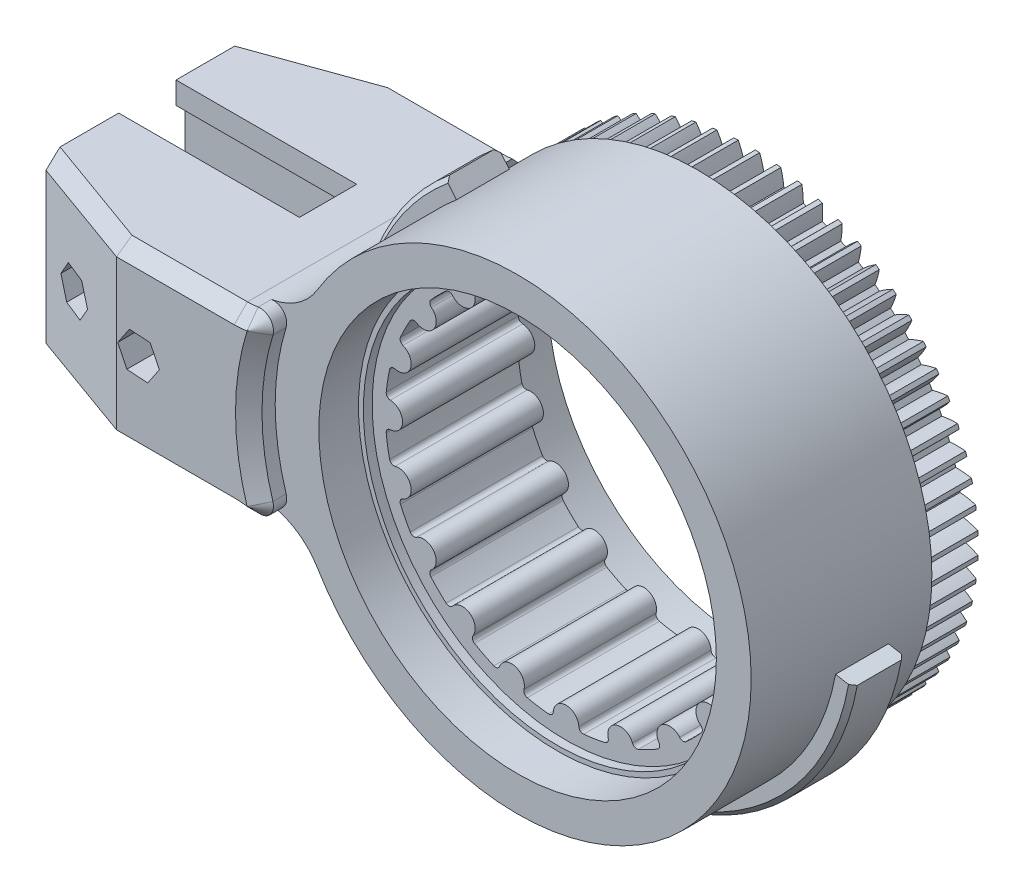
SolidWorks part; units mm, degrees
ref_plane "Front Plane" through (0, 0, 0) normal (0, 0, 1) x (1, 0, 0)
ref_plane "Top Plane" through (0, 0, 0) normal (0, 1, 0) x (1, 0, 0)
ref_plane "Right Plane" through (0, 0, 0) normal (1, 0, 0) x (0, 0, -1)
sketch "Sketch1" plane through (0, 0, 0) normal (0, 0, 1) x (1, 0, 0)
  circle A0 centre (0, 0) radius 53
  dimension "D1" = 106
extrude "Boss-Extrude1" add sketch "Sketch1" along normal blind 30
sketch "Sketch4" plane through (0, 0, 0) normal (0, 0, -1) x (-1, 0, 0)
  line L0 (53, 0) -> (110, 0) construction
  line L1 (49.0816, -20) -> (110, -20)
  line L2 (49.0816, 20) -> (110, 20)
  line L3 (110, 20) -> (110, -20)
  line L4 (0, 20) -> (110, 20) construction
  line L5 (0, 0) -> (110, 0) construction
  line L6 (0, -20) -> (110, -20) construction
  circle A0 centre (0, 0) radius 53 construction
  arc A1 (49.0816, -20) -> (49.0816, 20) centre (0, 0) ccw
  dimension "D3" = 110
  dimension "D1" = 20
  dimension "D2" = 20
extrude "Boss-Extrude2" add sketch "Sketch4" against normal up to surface (30 mm away) up to face at (53, 0, 30)
sketch "Sketch5" plane through (0, 0, 0) normal (0, 0, -1) x (-1, 0, 0)
  line L2 (110, -20) -> (110, 20)
  line L3 (110, 20) -> (51.2348, 20)
  line L5 (51.2348, -20) -> (110, -20)
  line L6 (0, 0) -> (139.0391, 0) construction
  arc A0 (51.2348, -20) -> (51.2348, 20) centre (0, 0) ccw
  dimension "D1" = 110
  dimension "D2" = 40
  dimension "D3" = 110
extrude "Boss-Extrude3" add sketch "Sketch5" along normal blind 17
sketch "Sketch6" plane through (0, 0, 30) normal (0, 0, 1) x (1, 0, 0)
  line L0 (-110, 0) -> (0, 0) construction
  line L6 (-110, -20) -> (-51.2348, -20)
  line L7 (-110, 20) -> (-110, -20)
  line L8 (-51.2348, 20) -> (-110, 20)
  arc A2 (-51.2348, 20) -> (-51.2348, -20) centre (0, 0) ccw
  dimension "D1" = 55
  dimension "D2" = 40
  dimension "D3" = 110
extrude "Boss-Extrude4" add sketch "Sketch6" along normal blind 17
sketch "Sketch7" plane through (0, 20, 0) normal (0, 1, 0) x (1, 0, 0)
  line L0 (53, -15) -> (-110, -15) construction
  line L1 (53, -30) -> (53, 0) construction
  line L2 (-110, -47) -> (-110, 17) construction
  line L4 (-151, -8.5) -> (-69, -8.5)
  line L5 (-151, -8.5) -> (-151, -21.5)
  line L6 (-151, -21.5) -> (-69, -21.5)
  line L7 (-69, -8.5) -> (-69, -21.5)
  line L8 (-151, -8.5) -> (-69, -21.5) construction
  line L9 (-151, -21.5) -> (-69, -8.5) construction
  dimension "D1" = 13
  dimension "D2" = 41
extrude "Cut-Extrude3" cut sketch "Sketch7" against normal through all
sketch "Sketch8" plane through (0, 20, 0) normal (0, 1, 0) x (1, 0, 0)
  line L0 (-110, 8) -> (-85, 17)
  line L1 (-110, -8.5) -> (-110, 17) construction
  line L2 (-110, 17) -> (-51.2348, 17) construction
  line L3 (-69, -15) -> (-102.4865, -15) construction
  line L4 (-69, -21.5) -> (-69, -8.5) construction
  line L5 (-110, -38) -> (-85, -47)
  line L6 (-110, -47) -> (-110, -21.5) construction
  line L7 (-51.2348, -47) -> (-110, -47) construction
  line L8 (-110, 17) -> (-85, 17)
  line L9 (-110, 8) -> (-110, 17)
  line L10 (-110, -47) -> (-110, -38)
  line L11 (-85, -47) -> (-110, -47)
  dimension "D1" = 9
  dimension "D2" = 25
extrude "Cut-Extrude4" cut sketch "Sketch8" against normal through all
fillet "Fillet3" radius 15 2 edges at (-49.0816, 20, 15) (-49.0816, -20, 15)
sketch "Sketch10" plane through (-110, 0, 0) normal (-1, 0, 0) x (0, 0, 1)
  line L0 (15, 20) -> (15, -20) construction
  line L1 (47, 20) -> (-17, 20) construction
  line L2 (-17, -20) -> (47, -20) construction
  line L3 (21.5, -20) -> (21.5, 20) construction
  line L4 (6.5, 15) -> (23.5, 15)
  line L5 (6.5, 15) -> (6.5, -15)
  line L6 (6.5, -15) -> (23.5, -15)
  line L7 (23.5, 15) -> (23.5, -15)
  line L8 (6.5, 15) -> (23.5, -15) construction
  line L9 (6.5, -15) -> (23.5, 15) construction
  point P6 (15, 0)
  dimension "D1" = 30
  dimension "D2" = 2
extrude "Cut-Extrude5" cut sketch "Sketch10" against normal blind 41
sketch "Sketch11" plane through (0, 0, -17) normal (0, 0, -1) x (-1, 0, 0)
  line L0 (110, 0) -> (45.4033, 0) construction
  line L1 (110, -20) -> (110, 20) construction
  circle A0 centre (100, 0) radius 2.75
  circle A1 centre (80, 0) radius 2.75
  dimension "D3" = 5.5
  dimension "D1" = 10
  dimension "D2" = 20
extrude "Cut-Extrude6" cut sketch "Sketch11" against normal through all
sketch "Sketch12" plane through (0, 0, -17) normal (0, 0, -1) x (-1, 0, 0)
  circle A0 centre (80, 0) radius 4.6
  circle A1 centre (100, 0) radius 4.6
  dimension "D1" = 9.2
extrude "Cut-Extrude7" cut sketch "Sketch12" against normal blind 12
sketch "Sketch13" plane through (0, 0, 47) normal (0, 0, 1) x (1, 0, 0)
  line L1 (-104.7224, 0.3346) -> (-102.651, -3.9225)
  line L2 (-102.651, -3.9225) -> (-97.9285, -4.257)
  line L3 (-97.9285, -4.257) -> (-95.2776, -0.3346)
  line L4 (-95.2776, -0.3346) -> (-97.349, 3.9225)
  line L5 (-97.349, 3.9225) -> (-102.0715, 4.257)
  line L6 (-102.0715, 4.257) -> (-104.7224, 0.3346)
  line L7 (-84.7224, 0.3346) -> (-82.651, -3.9225)
  line L8 (-82.651, -3.9225) -> (-77.9285, -4.257)
  line L9 (-77.9285, -4.257) -> (-75.2776, -0.3346)
  line L10 (-75.2776, -0.3346) -> (-77.349, 3.9225)
  line L11 (-77.349, 3.9225) -> (-82.0715, 4.257)
  line L12 (-82.0715, 4.257) -> (-84.7224, 0.3346)
  circle A0 centre (-100, 0) radius 4.1 construction
  circle A1 centre (-80, 0) radius 4.1 construction
  dimension "D1" = 8.2
extrude "Cut-Extrude8" cut sketch "Sketch13" against normal blind 12
sketch3d "3DSketch1"
  line L0 (-58.3009, 20, 47) -> (-85, 20, 47) construction
  line L1 (-85, -20, 47) -> (-85, 20, 47) construction
  point P0 (-54.8705, 20, 47)
  point P1 (-85, 11.3679, 47)
  point P4 (-110, 20, 38)
ref_plane "Plane2" through (0, 0, 15) normal (0, 0, 1) x (1, 0, 0)
fillet "Fillet5" radius 3 4 edges at (-50.2597, -22.3375, -8.5) (-50.2597, -22.3375, 38.5) (-50.2597, 22.3375, -8.5) (-50.2597, 22.3375, 38.5)
sketch "Sketch25" plane through (0, 0, 15) normal (0, 0, 1) x (1, 0, 0)
  circle A0 centre (0, 0) radius 57
  circle A1 centre (0, 0) radius 53
  arc A2 (-45.4404, -27.2794) -> (-45.4404, 27.2794) centre (0, 0) ccw construction
  dimension "D1" = 4
extrude "Boss-Extrude8" add sketch "Sketch25" along normal mid plane 12
sketch "Sketch26" plane through (0, 0, 21) normal (0, 0, 1) x (1, 0, 0)
  line L0 (56.0861, -10.1662) -> (52.1502, -9.4528)
  line L2 (-36.4297, 43.8392) -> (-33.8733, 40.7627)
  arc A0 (-53.0039, -20.9664) -> (-53.0039, 20.9664) centre (0, 0) ccw construction
  arc A1 (-45.4404, -27.2794) -> (-45.4404, 27.2794) centre (0, 0) ccw construction
  arc A2 (56.0861, -10.1662) -> (-36.4297, 43.8392) centre (0, 0) ccw
  arc A3 (52.1502, -9.4528) -> (-33.8733, 40.7627) centre (0, 0) ccw
  dimension "D1" = 140
extrude "Cut-Extrude12" cut sketch "Sketch26" against normal blind 15
chamfer "Chamfer4" distance 1 angle 45 4 edges at (5.6157, -56.7227, 21) (5.6157, -56.7227, 9) (-46.1561, 33.4457, 9) (-46.1561, 33.4457, 21)
sketch "Sketch27" plane through (0, 0, 30) normal (0, 0, 1) x (1, 0, 0)
  circle A0 centre (0, 0) radius 40 construction
  arc A1 (-40.9074, -2.7544) -> (-40.9074, 2.7544) centre (-40, 0) ccw
  arc A2 (-39.7564, 10.0215) -> (-38.0541, 15.2607) centre (-38.0423, 12.3607) ccw
  arc A3 (-34.7138, 21.8164) -> (-31.4758, 26.2731) centre (-32.3607, 23.5114) ccw
  arc A4 (-26.2731, 31.4758) -> (-21.8164, 34.7138) centre (-23.5114, 32.3607) ccw
  arc A5 (-15.2607, 38.0541) -> (-10.0215, 39.7564) centre (-12.3607, 38.0423) ccw
  arc A6 (-2.7544, 40.9074) -> (2.7544, 40.9074) centre (0, 40) ccw
  arc A7 (10.0215, 39.7564) -> (15.2607, 38.0541) centre (12.3607, 38.0423) ccw
  arc A8 (21.8164, 34.7138) -> (26.2731, 31.4758) centre (23.5114, 32.3607) ccw
  arc A9 (31.4758, 26.2731) -> (34.7138, 21.8164) centre (32.3607, 23.5114) ccw
  arc A10 (38.0541, 15.2607) -> (39.7564, 10.0215) centre (38.0423, 12.3607) ccw
  arc A11 (40.9074, 2.7544) -> (40.9074, -2.7544) centre (40, 0) ccw
  arc A12 (39.7564, -10.0215) -> (38.0541, -15.2607) centre (38.0423, -12.3607) ccw
  arc A13 (34.7138, -21.8164) -> (31.4758, -26.2731) centre (32.3607, -23.5114) ccw
  arc A14 (26.2731, -31.4758) -> (21.8164, -34.7138) centre (23.5114, -32.3607) ccw
  arc A15 (15.2607, -38.0541) -> (10.0215, -39.7564) centre (12.3607, -38.0423) ccw
  arc A16 (2.7544, -40.9074) -> (-2.7544, -40.9074) centre (0, -40) ccw
  arc A17 (26.2731, -31.4758) -> (31.4758, -26.2731) centre (0, 0) ccw
  arc A18 (34.7138, -21.8164) -> (38.0541, -15.2607) centre (0, 0) ccw
  arc A19 (39.7564, -10.0215) -> (40.9074, -2.7544) centre (0, 0) ccw
  arc A20 (40.9074, 2.7544) -> (39.7564, 10.0215) centre (0, 0) ccw
  arc A21 (38.0541, 15.2607) -> (34.7138, 21.8164) centre (0, 0) ccw
  arc A22 (31.4758, 26.2731) -> (26.2731, 31.4758) centre (0, 0) ccw
  arc A23 (21.8164, 34.7138) -> (15.2607, 38.0541) centre (0, 0) ccw
  arc A24 (10.0215, 39.7564) -> (2.7544, 40.9074) centre (0, 0) ccw
  arc A25 (-2.7544, 40.9074) -> (-10.0215, 39.7564) centre (0, 0) ccw
  arc A26 (-15.2607, 38.0541) -> (-21.8164, 34.7138) centre (0, 0) ccw
  arc A27 (-26.2731, 31.4758) -> (-31.4758, 26.2731) centre (0, 0) ccw
  arc A28 (-34.7138, 21.8164) -> (-38.0541, 15.2607) centre (0, 0) ccw
  arc A29 (-39.7564, 10.0215) -> (-40.9074, 2.7544) centre (0, 0) ccw
  arc A30 (-40.9074, -2.7544) -> (-2.7544, -40.9074) centre (0, 0) ccw
  arc A31 (2.7544, -40.9074) -> (10.0215, -39.7564) centre (0, 0) ccw
  arc A32 (15.2607, -38.0541) -> (21.8164, -34.7138) centre (0, 0) ccw
  arc A33 (-10.0215, -39.7564) -> (-15.2607, -38.0541) centre (-12.3607, -38.0423) ccw
  arc A34 (-21.8164, -34.7138) -> (-26.2731, -31.4758) centre (-23.5114, -32.3607) ccw
  arc A35 (-31.4758, -26.2731) -> (-34.7138, -21.8164) centre (-32.3607, -23.5114) ccw
  arc A36 (-38.0541, -15.2607) -> (-39.7564, -10.0215) centre (-38.0423, -12.3607) ccw
  point P35 (0, 0)
  point P38 (0, 0)
  dimension "D1" = 80
  dimension "D2" = 5.8
  dimension "D4" = 41
  dimension "D3" = 20
extrude "Cut-Extrude13" cut sketch "Sketch27" against normal through all contours A36 A30 A35 A34 A33 A16 A31 A15 A32 A14 A17 A13 A18 A12 A19 A11 A20 A10 A21 A9 A22 A8 A23 A7 A24 A6 A25 A5 A26 A4 A27 A3 A28 A2 A29 A1 region at (0, 0, 30)
fillet "Fillet6" radius 1 40 edges at (2.7544, 40.9074, 15) (38.0541, -15.2607, 15) (31.4758, -26.2731, 15) (21.8164, -34.7138, 15) (10.0215, -39.7564, 15) (-2.7544, -40.9074, 15) (-15.2607, -38.0541, 15) (-26.2731, -31.4758, 15) (-34.7138, -21.8164, 15) (-40.9074, 2.7544, 15) (-40.9074, -2.7544, 15) (-39.7564, 10.0215, 15) (-38.0541, 15.2607, 15) (-31.4758, 26.2731, 15) (-34.7138, 21.8164, 15) (-26.2731, 31.4758, 15) (-21.8164, 34.7138, 15) (-10.0215, 39.7564, 15) (-15.2607, 38.0541, 15) (-2.7544, 40.9074, 15) (10.0215, 39.7564, 15) (15.2607, 38.0541, 15) (21.8164, 34.7138, 15) (26.2731, 31.4758, 15) (31.4758, 26.2731, 15) (34.7138, 21.8164, 15) (38.0541, 15.2607, 15) (39.7564, 10.0215, 15) (40.9074, 2.7544, 15) (40.9074, -2.7544, 15) (39.7564, -10.0215, 15) (34.7138, -21.8164, 15) (26.2731, -31.4758, 15) (-39.7564, -10.0215, 15) (15.2607, -38.0541, 15) (2.7544, -40.9074, 15) (-10.0215, -39.7564, 15) (-21.8164, -34.7138, 15) (-31.4758, -26.2731, 15) (-38.0541, -15.2607, 15)
sketch "Sketch28" plane through (0, 0, 30) normal (0, 0, 1) x (1, 0, 0)
  arc A0 (-45.4404, 27.2794) -> (-45.4404, -27.2794) centre (0, 0) ccw
  arc A7 (-52.5145, 16.3471) -> (-52.5145, -16.3471) centre (0, 0) ccw
  arc A8 (-55.8659, -20.199) -> (-52.5145, -16.3471) centre (-55.3789, -17.2388) ccw
  arc A9 (-45.4404, -27.2794) -> (-55.8659, -20.199) centre (-58.3009, -35) ccw
  arc A10 (-45.4404, -27.2794) -> (-45.4404, 27.2794) centre (0, 0) ccw
  arc A11 (-55.8659, 20.199) -> (-45.4404, 27.2794) centre (-58.3009, 35) ccw
  arc A12 (-52.5145, 16.3471) -> (-55.8659, 20.199) centre (-55.3789, 17.2388) ccw
  arc A13 (-52.5145, 16.3471) -> (-52.5145, -16.3471) centre (0, 0) ccw
  arc A14 (-55.8659, -20.199) -> (-52.5145, -16.3471) centre (-55.3789, -17.2388) ccw
  arc A15 (-45.4404, -27.2794) -> (-55.8659, -20.199) centre (-58.3009, -35) ccw
  arc A17 (-55.8659, 20.199) -> (-45.4404, 27.2794) centre (-58.3009, 35) ccw
  arc A18 (-52.5145, 16.3471) -> (-55.8659, 20.199) centre (-55.3789, 17.2388) ccw
  dimension "D1" = 0
extrude "Boss-Extrude9" add sketch "Sketch28" along normal up to surface (17 mm away) up to face at (-80, 0, 47)
sketch "Sketch29" plane through (0, 0, 30) normal (0, 0, 1) x (1, 0, 0)
  circle A0 centre (0, 0) radius 53
  circle A1 centre (0, 0) radius 44
  arc A2 (-45.4404, -27.2794) -> (-45.4404, 27.2794) centre (0, 0) ccw construction
  dimension "D1" = 88
extrude "Boss-Extrude10" add sketch "Sketch29" along normal blind 11
sketch "Sketch30" plane through (0, 0, 41) normal (0, 0, 1) x (1, 0, 0)
  circle A0 centre (0, 0) radius 45.1
  dimension "D1" = 90.2
extrude "Cut-Extrude14" cut sketch "Sketch30" against normal blind 9
sketch "Sketch31" plane through (0, 0, 0) normal (0, 0, -1) x (-1, 0, 0)
  arc A6 (52.5145, -16.3471) -> (52.5145, 16.3471) centre (0, 0) ccw
  arc A7 (55.8659, 20.199) -> (52.5145, 16.3471) centre (55.3789, 17.2388) ccw
  arc A8 (45.4404, 27.2794) -> (55.8659, 20.199) centre (58.3009, 35) ccw
  arc A9 (45.4404, 27.2794) -> (45.4404, -27.2794) centre (0, 0) ccw
  arc A10 (55.8659, -20.199) -> (45.4404, -27.2794) centre (58.3009, -35) ccw
  arc A11 (52.5145, -16.3471) -> (55.8659, -20.199) centre (55.3789, -17.2388) ccw
  arc A12 (52.5145, -16.3471) -> (52.5145, 16.3471) centre (0, 0) ccw
  arc A13 (55.8659, 20.199) -> (52.5145, 16.3471) centre (55.3789, 17.2388) ccw
  arc A14 (45.4404, 27.2794) -> (55.8659, 20.199) centre (58.3009, 35) ccw
  arc A15 (45.4404, 27.2794) -> (45.4404, -27.2794) centre (0, 0) ccw
  arc A16 (55.8659, -20.199) -> (45.4404, -27.2794) centre (58.3009, -35) ccw
  arc A17 (52.5145, -16.3471) -> (55.8659, -20.199) centre (55.3789, -17.2388) ccw
  circle A24 centre (0, 0) radius 44
  dimension "D2" = 88
  dimension "D1" = 0
extrude "Boss-Extrude12" add sketch "Sketch31" along normal blind 11
sketch "Sketch32" plane through (0, 0, -11) normal (0, 0, -1) x (-1, 0, 0)
  circle A0 centre (0, 0) radius 45.1
  dimension "D1" = 90.2
extrude "Cut-Extrude15" cut sketch "Sketch32" against normal blind 9
sketch "Sketch33" plane through (0, 0, 41) normal (0, 0, 1) x (1, 0, 0)
  arc A6 (-55.8659, -20.199) -> (-52.5145, -16.3471) centre (-55.3789, -17.2388) ccw
  arc A7 (-52.5145, 16.3471) -> (-52.5145, -16.3471) centre (0, 0) ccw
  arc A8 (-52.5145, 16.3471) -> (-55.8659, 20.199) centre (-55.3789, 17.2388) ccw
  arc A9 (-55.8659, 20.199) -> (-45.4404, 27.2794) centre (-58.3009, 35) ccw
  arc A10 (-45.4404, -27.2794) -> (-45.4404, 27.2794) centre (0, 0) ccw
  arc A11 (-45.4404, -27.2794) -> (-55.8659, -20.199) centre (-58.3009, -35) ccw
  arc A12 (-55.8659, -20.199) -> (-52.5145, -16.3471) centre (-55.3789, -17.2388) ccw
  arc A13 (-52.5145, 16.3471) -> (-52.5145, -16.3471) centre (0, 0) ccw
  arc A14 (-52.5145, 16.3471) -> (-55.8659, 20.199) centre (-55.3789, 17.2388) ccw
  arc A15 (-55.8659, 20.199) -> (-45.4404, 27.2794) centre (-58.3009, 35) ccw
  arc A16 (-45.4404, -27.2794) -> (-45.4404, 27.2794) centre (0, 0) ccw
  arc A17 (-45.4404, -27.2794) -> (-55.8659, -20.199) centre (-58.3009, -35) ccw
  dimension "D1" = 0
extrude "Cut-Extrude16" cut sketch "Sketch33" along normal blind 87
sketch "Sketch34" plane through (0, 0, -11) normal (0, 0, -1) x (-1, 0, 0)
  line L0 (43.5903, -29.2582) -> (46.7331, -25.4509)
  line L1 (43.0288, 30.0782) -> (46.5882, 25.6292)
  line L2 (-0.0007, 0.0006) -> (24.1488, 0.0006) construction
  line L3 (43.0288, -30.077) -> (46.5882, -25.628)
  line L4 (46.7331, -25.4509) -> (28.204, -92.7872)
  line L5 (28.204, -92.7872) -> (-81.3353, -44.683)
  line L6 (-81.3353, -44.683) -> (-81.3353, 38.0689)
  line L7 (-81.3353, 38.0689) -> (11.5354, 66.4741)
  line L8 (11.5354, 66.4741) -> (65.3005, 45.6222)
  line L9 (65.3005, 45.6222) -> (46.5882, 25.6292)
  circle A0 centre (-0.0007, 0.0006) radius 51 construction
  arc A1 (-49.1207, -0.6313) -> (-52.4653, -1.928) centre (-43.4473, -20.2265) ccw
  arc A2 (-52.4653, -1.928) -> (-52.4194, -2.9198) centre (-0.0007, 0.0006) ccw
  arc A3 (-52.4194, -2.9198) -> (-48.9694, -3.9024) centre (-45.1283, 16.1327) ccw
  arc A4 (-48.9694, -3.9024) -> (-48.8528, -5.1608) centre (-0.0007, 0.0006) ccw
  arc A5 (-48.8528, -5.1608) -> (-52.0635, -6.7606) centre (-41.3956, -24.149) ccw
  arc A6 (-52.0635, -6.7606) -> (-51.9264, -7.744) centre (-0.0007, 0.0006) ccw
  arc A7 (-51.9264, -7.744) -> (-48.4004, -8.404) centre (-46.4243, 11.9) ccw
  arc A8 (-48.4004, -8.404) -> (-48.1682, -9.6463) centre (-0.0007, 0.0006) ccw
  arc A9 (-48.1682, -9.6463) -> (-51.2176, -11.5355) centre (-38.9908, -27.8654) ccw
  arc A10 (-51.2176, -11.5355) -> (-50.9903, -12.502) centre (-0.0007, 0.0006) ccw
  arc A11 (-50.9903, -12.502) -> (-47.4185, -12.8339) centre (-47.3242, 7.5659) ccw
  arc A12 (-47.4185, -12.8339) -> (-47.0726, -14.0495) centre (-0.0007, 0.0006) ccw
  arc A13 (-47.0726, -14.0495) -> (-49.9347, -16.212) centre (-36.2533, -31.3441) ccw
  arc A14 (-49.9347, -16.212) -> (-49.6192, -17.1534) centre (-0.0007, 0.0006) ccw
  arc A15 (-49.6192, -17.1534) -> (-46.032, -17.1543) centre (-47.8203, 3.1671) ccw
  arc A16 (-46.032, -17.1543) -> (-45.5754, -18.3328) centre (-0.0007, 0.0006) ccw
  arc A17 (-45.5754, -18.3328) -> (-48.2258, -20.7502) centre (-33.2066, -34.5553) ccw
  arc A18 (-48.2258, -20.7502) -> (-47.8247, -21.6584) centre (-0.0007, 0.0006) ccw
  arc A19 (-47.8247, -21.6584) -> (-44.2528, -21.3284) centre (-47.9085, -1.2586) ccw
  arc A20 (-44.2528, -21.3284) -> (-43.6894, -22.4597) centre (-0.0007, 0.0006) ccw
  arc A21 (-43.6894, -22.4597) -> (-46.1054, -25.1113) centre (-29.8765, -37.4718) ccw
  arc A22 (-46.1054, -25.1113) -> (-45.6223, -25.9787) centre (-0.0007, 0.0006) ccw
  arc A23 (-45.6223, -25.9787) -> (-42.096, -25.3205) centre (-47.588, -5.6736) ccw
  arc A24 (-42.096, -25.3205) -> (-41.4307, -26.395) centre (-0.0007, 0.0006) ccw
  arc A25 (-41.4307, -26.395) -> (-43.5917, -29.2582) centre (-26.2915, -40.0685) ccw
  arc A26 (-43.5917, -29.2582) -> (-43.0306, -30.0773) centre (-0.0007, 0.0006) ccw
  arc A27 (-43.0306, -30.0773) -> (-39.5801, -29.0965) centre (-46.8614, -10.0402) ccw
  arc A28 (-39.5801, -29.0965) -> (-38.8185, -30.105) centre (-0.0007, 0.0006) ccw
  arc A29 (-38.8185, -30.105) -> (-40.7061, -33.1554) centre (-22.4823, -42.3234) ccw
  arc A30 (-40.7061, -33.1554) -> (-40.0718, -33.9193) centre (-0.0007, 0.0006) ccw
  arc A31 (-40.0718, -33.9193) -> (-36.7265, -32.6243) centre (-45.7351, -14.3211) ccw
  arc A32 (-36.7265, -32.6243) -> (-35.8751, -33.5583) centre (-0.0007, 0.0006) ccw
  arc A33 (-35.8751, -33.5583) -> (-37.4732, -36.7698) centre (-18.4812, -44.2172) ccw
  arc A34 (-37.4732, -36.7698) -> (-36.7711, -37.4719) centre (-0.0007, 0.0006) ccw
  arc A35 (-36.7711, -37.4719) -> (-33.5596, -35.8738) centre (-44.2185, -18.4799) ccw
  arc A36 (-33.5596, -35.8738) -> (-32.6256, -36.7252) centre (-0.0007, 0.0006) ccw
  arc A37 (-32.6256, -36.7252) -> (-33.9206, -40.0705) centre (-14.3225, -45.7337) ccw
  arc A38 (-33.9206, -40.0705) -> (-33.1568, -40.7048) centre (-0.0007, 0.0006) ccw
  arc A39 (-33.1568, -40.7048) -> (-30.1064, -38.8171) centre (-42.3247, -22.4809) ccw
  arc A40 (-30.1064, -38.8171) -> (-29.0978, -39.5788) centre (-0.0007, 0.0006) ccw
  arc A41 (-29.0978, -39.5788) -> (-30.0786, -43.0293) centre (-10.0415, -46.8601) ccw
  arc A42 (-30.0786, -43.0293) -> (-29.2595, -43.5904) centre (-0.0007, 0.0006) ccw
  arc A43 (-29.2595, -43.5904) -> (-26.3963, -41.4294) centre (-40.0699, -26.2902) ccw
  arc A44 (-26.3963, -41.4294) -> (-25.3218, -42.0947) centre (-0.0007, 0.0006) ccw
  arc A45 (-25.3218, -42.0947) -> (-25.98, -45.6209) centre (-5.675, -47.5866) ccw
  arc A46 (-25.98, -45.6209) -> (-25.1126, -46.1041) centre (-0.0007, 0.0006) ccw
  arc A47 (-25.1126, -46.1041) -> (-22.461, -43.6881) centre (-37.4731, -29.8752) ccw
  arc A48 (-22.461, -43.6881) -> (-21.3297, -44.2514) centre (-0.0007, 0.0006) ccw
  arc A49 (-21.3297, -44.2514) -> (-21.6598, -47.8234) centre (-1.26, -47.9072) ccw
  arc A50 (-21.6598, -47.8234) -> (-20.7515, -48.2244) centre (-0.0007, 0.0006) ccw
  arc A51 (-20.7515, -48.2244) -> (-18.3341, -45.5741) centre (-34.5567, -33.2052) ccw
  arc A52 (-18.3341, -45.5741) -> (-17.1557, -46.0306) centre (-0.0007, 0.0006) ccw
  arc A53 (-17.1557, -46.0306) -> (-17.1547, -49.6178) centre (3.1658, -47.819) ccw
  arc A54 (-17.1547, -49.6178) -> (-16.2133, -49.9334) centre (-0.0007, 0.0006) ccw
  arc A55 (-16.2133, -49.9334) -> (-14.0508, -47.0713) centre (-31.3454, -36.252) ccw
  arc A56 (-14.0508, -47.0713) -> (-12.8353, -47.4171) centre (-0.0007, 0.0006) ccw
  arc A57 (-12.8353, -47.4171) -> (-12.5034, -50.9889) centre (7.5645, -47.3228) ccw
  arc A58 (-12.5034, -50.9889) -> (-11.5368, -51.2163) centre (-0.0007, 0.0006) ccw
  arc A59 (-11.5368, -51.2163) -> (-9.6476, -48.1669) centre (-27.8667, -38.9895) ccw
  arc A60 (-9.6476, -48.1669) -> (-8.4054, -48.3991) centre (-0.0007, 0.0006) ccw
  arc A61 (-8.4054, -48.3991) -> (-7.7453, -51.925) centre (11.8987, -46.4229) ccw
  arc A62 (-7.7453, -51.925) -> (-6.7619, -52.0622) centre (-0.0007, 0.0006) ccw
  arc A63 (-6.7619, -52.0622) -> (-5.1622, -48.8515) centre (-24.1503, -41.3943) ccw
  arc A64 (-5.1622, -48.8515) -> (-3.9037, -48.9681) centre (-0.0007, 0.0006) ccw
  arc A65 (-3.9037, -48.9681) -> (-2.9212, -52.4181) centre (16.1314, -45.1269) ccw
  arc A66 (-2.9212, -52.4181) -> (-1.9293, -52.464) centre (-0.0007, 0.0006) ccw
  arc A67 (-1.9293, -52.464) -> (-0.6326, -49.1193) centre (-20.2279, -43.446) ccw
  arc A68 (-0.6326, -49.1193) -> (0.6312, -49.1193) centre (-0.0007, 0.0006) ccw
  arc A69 (0.6312, -49.1193) -> (1.9279, -52.464) centre (20.2264, -43.446) ccw
  arc A70 (1.9279, -52.464) -> (2.9197, -52.4181) centre (-0.0007, 0.0006) ccw
  arc A71 (2.9197, -52.4181) -> (3.9023, -48.9681) centre (-16.1328, -45.1269) ccw
  arc A72 (3.9023, -48.9681) -> (5.1607, -48.8515) centre (-0.0007, 0.0006) ccw
  arc A73 (5.1607, -48.8515) -> (6.7605, -52.0622) centre (24.1488, -41.3943) ccw
  arc A74 (6.7605, -52.0622) -> (7.7438, -51.925) centre (-0.0007, 0.0006) ccw
  arc A75 (7.7438, -51.925) -> (8.4039, -48.3991) centre (-11.9002, -46.4229) ccw
  arc A76 (8.4039, -48.3991) -> (9.6462, -48.1669) centre (-0.0007, 0.0006) ccw
  arc A77 (9.6462, -48.1669) -> (11.5354, -51.2163) centre (27.8653, -38.9895) ccw
  arc A78 (11.5354, -51.2163) -> (12.5019, -50.9889) centre (-0.0007, 0.0006) ccw
  arc A79 (12.5019, -50.9889) -> (12.8338, -47.4171) centre (-7.566, -47.3228) ccw
  arc A80 (12.8338, -47.4171) -> (14.0493, -47.0713) centre (-0.0007, 0.0006) ccw
  arc A81 (14.0493, -47.0713) -> (16.2119, -49.9334) centre (31.344, -36.252) ccw
  arc A82 (16.2119, -49.9334) -> (17.1533, -49.6178) centre (-0.0007, 0.0006) ccw
  arc A83 (17.1533, -49.6178) -> (17.1542, -46.0306) centre (-3.1673, -47.819) ccw
  arc A84 (17.1542, -46.0306) -> (18.3327, -45.5741) centre (-0.0007, 0.0006) ccw
  arc A85 (18.3327, -45.5741) -> (20.75, -48.2244) centre (34.5552, -33.2052) ccw
  arc A86 (20.75, -48.2244) -> (21.6583, -47.8234) centre (-0.0007, 0.0006) ccw
  arc A87 (21.6583, -47.8234) -> (21.3283, -44.2514) centre (1.2585, -47.9072) ccw
  arc A88 (21.3283, -44.2514) -> (22.4596, -43.6881) centre (-0.0007, 0.0006) ccw
  arc A89 (22.4596, -43.6881) -> (25.1112, -46.1041) centre (37.4716, -29.8752) ccw
  arc A90 (25.1112, -46.1041) -> (25.9786, -45.6209) centre (-0.0007, 0.0006) ccw
  arc A91 (25.9786, -45.6209) -> (25.3203, -42.0947) centre (5.6735, -47.5866) ccw
  arc A92 (25.3203, -42.0947) -> (26.3948, -41.4294) centre (-0.0007, 0.0006) ccw
  arc A93 (26.3948, -41.4294) -> (29.258, -43.5904) centre (40.0684, -26.2902) ccw
  arc A94 (29.258, -43.5904) -> (30.0772, -43.0293) centre (-0.0007, 0.0006) ccw
  arc A95 (30.0772, -43.0293) -> (29.0964, -39.5788) centre (10.0401, -46.8601) ccw
  arc A96 (29.0964, -39.5788) -> (30.1049, -38.8171) centre (-0.0007, 0.0006) ccw
  arc A97 (30.1049, -38.8171) -> (33.1553, -40.7048) centre (42.3233, -22.4809) ccw
  arc A98 (33.1553, -40.7048) -> (33.9192, -40.0705) centre (-0.0007, 0.0006) ccw
  arc A99 (33.9192, -40.0705) -> (32.6242, -36.7252) centre (14.321, -45.7337) ccw
  arc A100 (32.6242, -36.7252) -> (33.5581, -35.8738) centre (-0.0007, 0.0006) ccw
  arc A101 (33.5581, -35.8738) -> (36.7697, -37.4719) centre (44.2171, -18.4799) ccw
  arc A102 (36.7697, -37.4719) -> (37.4718, -36.7698) centre (-0.0007, 0.0006) ccw
  arc A103 (37.4718, -36.7698) -> (35.8736, -33.5583) centre (18.4797, -44.2172) ccw
  arc A104 (35.8736, -33.5583) -> (36.725, -32.6243) centre (-0.0007, 0.0006) ccw
  arc A105 (36.725, -32.6243) -> (40.0703, -33.9193) centre (45.7336, -14.3211) ccw
  arc A106 (40.0703, -33.9193) -> (40.7046, -33.1554) centre (-0.0007, 0.0006) ccw
  arc A107 (40.7046, -33.1554) -> (38.817, -30.105) centre (22.4808, -42.3234) ccw
  arc A108 (38.817, -30.105) -> (39.5786, -29.0965) centre (-0.0007, 0.0006) ccw
  arc A109 (39.5786, -29.0965) -> (43.0291, -30.0773) centre (46.8599, -10.0402) ccw
  arc A110 (43.0291, -30.0773) -> (43.5903, -29.2582) centre (-0.0007, 0.0006) ccw
  arc A163 (43.0288, 30.0782) -> (39.5786, 29.0977) centre (46.8588, 10.041) ccw
  arc A164 (39.5786, 29.0977) -> (38.817, 30.1062) centre (-0.0007, 0.0006) ccw
  arc A165 (38.817, 30.1062) -> (40.7046, 33.1566) centre (22.4808, 42.3246) ccw
  arc A166 (40.7046, 33.1566) -> (40.0703, 33.9205) centre (-0.0007, 0.0006) ccw
  arc A167 (40.0703, 33.9205) -> (36.725, 32.6255) centre (45.7336, 14.3223) ccw
  arc A168 (36.725, 32.6255) -> (35.8736, 33.5595) centre (-0.0007, 0.0006) ccw
  arc A169 (35.8736, 33.5595) -> (37.4718, 36.771) centre (18.4797, 44.2184) ccw
  arc A170 (37.4718, 36.771) -> (36.7697, 37.4731) centre (-0.0007, 0.0006) ccw
  arc A171 (36.7697, 37.4731) -> (33.5581, 35.875) centre (44.2171, 18.4811) ccw
  arc A172 (33.5581, 35.875) -> (32.6242, 36.7264) centre (-0.0007, 0.0006) ccw
  arc A173 (32.6242, 36.7264) -> (33.9192, 40.0717) centre (14.321, 45.7349) ccw
  arc A174 (33.9192, 40.0717) -> (33.1553, 40.706) centre (-0.0007, 0.0006) ccw
  arc A175 (33.1553, 40.706) -> (30.1049, 38.8184) centre (42.3233, 22.4821) ccw
  arc A176 (30.1049, 38.8184) -> (29.0964, 39.58) centre (-0.0007, 0.0006) ccw
  arc A177 (29.0964, 39.58) -> (30.0772, 43.0305) centre (10.0401, 46.8613) ccw
  arc A178 (30.0772, 43.0305) -> (29.258, 43.5916) centre (-0.0007, 0.0006) ccw
  arc A179 (29.258, 43.5916) -> (26.3948, 41.4306) centre (40.0684, 26.2914) ccw
  arc A180 (26.3948, 41.4306) -> (25.3203, 42.0959) centre (-0.0007, 0.0006) ccw
  arc A181 (25.3203, 42.0959) -> (25.9786, 45.6222) centre (5.6735, 47.5878) ccw
  arc A182 (25.9786, 45.6222) -> (25.1112, 46.1053) centre (-0.0007, 0.0006) ccw
  arc A183 (25.1112, 46.1053) -> (22.4596, 43.6893) centre (37.4716, 29.8764) ccw
  arc A184 (22.4596, 43.6893) -> (21.3283, 44.2526) centre (-0.0007, 0.0006) ccw
  arc A185 (21.3283, 44.2526) -> (21.6583, 47.8246) centre (1.2585, 47.9084) ccw
  arc A186 (21.6583, 47.8246) -> (20.75, 48.2257) centre (-0.0007, 0.0006) ccw
  arc A187 (20.75, 48.2257) -> (18.3327, 45.5753) centre (34.5552, 33.2064) ccw
  arc A188 (18.3327, 45.5753) -> (17.1542, 46.0319) centre (-0.0007, 0.0006) ccw
  arc A189 (17.1542, 46.0319) -> (17.1533, 49.619) centre (-3.1673, 47.8202) ccw
  arc A190 (17.1533, 49.619) -> (16.2119, 49.9346) centre (-0.0007, 0.0006) ccw
  arc A191 (16.2119, 49.9346) -> (14.0493, 47.0725) centre (31.344, 36.2532) ccw
  arc A192 (14.0493, 47.0725) -> (12.8338, 47.4183) centre (-0.0007, 0.0006) ccw
  arc A193 (12.8338, 47.4183) -> (12.5019, 50.9902) centre (-7.566, 47.324) ccw
  arc A194 (12.5019, 50.9902) -> (11.5354, 51.2175) centre (-0.0007, 0.0006) ccw
  arc A195 (11.5354, 51.2175) -> (9.6462, 48.1681) centre (27.8653, 38.9907) ccw
  arc A196 (9.6462, 48.1681) -> (8.4039, 48.4003) centre (-0.0007, 0.0006) ccw
  arc A197 (8.4039, 48.4003) -> (7.7438, 51.9262) centre (-11.9002, 46.4241) ccw
  arc A198 (7.7438, 51.9262) -> (6.7605, 52.0634) centre (-0.0007, 0.0006) ccw
  arc A199 (6.7605, 52.0634) -> (5.1607, 48.8527) centre (24.1488, 41.3955) ccw
  arc A200 (5.1607, 48.8527) -> (3.9023, 48.9693) centre (-0.0007, 0.0006) ccw
  arc A201 (3.9023, 48.9693) -> (2.9197, 52.4193) centre (-16.1328, 45.1282) ccw
  arc A202 (2.9197, 52.4193) -> (1.9279, 52.4652) centre (-0.0007, 0.0006) ccw
  arc A203 (1.9279, 52.4652) -> (0.6312, 49.1205) centre (20.2264, 43.4472) ccw
  arc A204 (0.6312, 49.1205) -> (-0.6326, 49.1205) centre (-0.0007, 0.0006) ccw
  arc A205 (-0.6326, 49.1205) -> (-1.9293, 52.4652) centre (-20.2279, 43.4472) ccw
  arc A206 (-1.9293, 52.4652) -> (-2.9212, 52.4193) centre (-0.0007, 0.0006) ccw
  arc A207 (-2.9212, 52.4193) -> (-3.9037, 48.9693) centre (16.1314, 45.1282) ccw
  arc A208 (-3.9037, 48.9693) -> (-5.1622, 48.8527) centre (-0.0007, 0.0006) ccw
  arc A209 (-5.1622, 48.8527) -> (-6.7619, 52.0634) centre (-24.1503, 41.3955) ccw
  arc A210 (-6.7619, 52.0634) -> (-7.7453, 51.9262) centre (-0.0007, 0.0006) ccw
  arc A211 (-7.7453, 51.9262) -> (-8.4054, 48.4003) centre (11.8987, 46.4241) ccw
  arc A212 (-8.4054, 48.4003) -> (-9.6476, 48.1681) centre (-0.0007, 0.0006) ccw
  arc A213 (-9.6476, 48.1681) -> (-11.5368, 51.2175) centre (-27.8667, 38.9907) ccw
  arc A214 (-11.5368, 51.2175) -> (-12.5034, 50.9902) centre (-0.0007, 0.0006) ccw
  arc A215 (-12.5034, 50.9902) -> (-12.8353, 47.4183) centre (7.5645, 47.324) ccw
  arc A216 (-12.8353, 47.4183) -> (-14.0508, 47.0725) centre (-0.0007, 0.0006) ccw
  arc A217 (-14.0508, 47.0725) -> (-16.2133, 49.9346) centre (-31.3454, 36.2532) ccw
  arc A218 (-16.2133, 49.9346) -> (-17.1547, 49.619) centre (-0.0007, 0.0006) ccw
  arc A219 (-17.1547, 49.619) -> (-17.1557, 46.0319) centre (3.1658, 47.8202) ccw
  arc A220 (-17.1557, 46.0319) -> (-18.3341, 45.5753) centre (-0.0007, 0.0006) ccw
  arc A221 (-18.3341, 45.5753) -> (-20.7515, 48.2257) centre (-34.5567, 33.2064) ccw
  arc A222 (-20.7515, 48.2257) -> (-21.6598, 47.8246) centre (-0.0007, 0.0006) ccw
  arc A223 (-21.6598, 47.8246) -> (-21.3297, 44.2526) centre (-1.26, 47.9084) ccw
  arc A224 (-21.3297, 44.2526) -> (-22.461, 43.6893) centre (-0.0007, 0.0006) ccw
  arc A225 (-22.461, 43.6893) -> (-25.1126, 46.1053) centre (-37.4731, 29.8764) ccw
  arc A226 (-25.1126, 46.1053) -> (-25.98, 45.6222) centre (-0.0007, 0.0006) ccw
  arc A227 (-25.98, 45.6222) -> (-25.3218, 42.0959) centre (-5.675, 47.5878) ccw
  arc A228 (-25.3218, 42.0959) -> (-26.3963, 41.4306) centre (-0.0007, 0.0006) ccw
  arc A229 (-26.3963, 41.4306) -> (-29.2595, 43.5916) centre (-40.0699, 26.2914) ccw
  arc A230 (-29.2595, 43.5916) -> (-30.0786, 43.0305) centre (-0.0007, 0.0006) ccw
  arc A231 (-30.0786, 43.0305) -> (-29.0978, 39.58) centre (-10.0415, 46.8613) ccw
  arc A232 (-29.0978, 39.58) -> (-30.1064, 38.8184) centre (-0.0007, 0.0006) ccw
  arc A233 (-30.1064, 38.8184) -> (-33.1568, 40.706) centre (-42.3247, 22.4821) ccw
  arc A234 (-33.1568, 40.706) -> (-33.9206, 40.0717) centre (-0.0007, 0.0006) ccw
  arc A235 (-33.9206, 40.0717) -> (-32.6256, 36.7264) centre (-14.3225, 45.7349) ccw
  arc A236 (-32.6256, 36.7264) -> (-33.5596, 35.875) centre (-0.0007, 0.0006) ccw
  arc A237 (-33.5596, 35.875) -> (-36.7711, 37.4731) centre (-44.2185, 18.4811) ccw
  arc A238 (-36.7711, 37.4731) -> (-37.4732, 36.771) centre (-0.0007, 0.0006) ccw
  arc A239 (-37.4732, 36.771) -> (-35.8751, 33.5595) centre (-18.4812, 44.2184) ccw
  arc A240 (-35.8751, 33.5595) -> (-36.7265, 32.6255) centre (-0.0007, 0.0006) ccw
  arc A241 (-36.7265, 32.6255) -> (-40.0718, 33.9205) centre (-45.7351, 14.3223) ccw
  arc A242 (-40.0718, 33.9205) -> (-40.7061, 33.1566) centre (-0.0007, 0.0006) ccw
  arc A243 (-40.7061, 33.1566) -> (-38.8185, 30.1062) centre (-22.4823, 42.3246) ccw
  arc A244 (-38.8185, 30.1062) -> (-39.5801, 29.0977) centre (-0.0007, 0.0006) ccw
  arc A245 (-39.5801, 29.0977) -> (-43.0306, 30.0785) centre (-46.8614, 10.0414) ccw
  arc A246 (-43.0306, 30.0785) -> (-43.5917, 29.2594) centre (-0.0007, 0.0006) ccw
  arc A247 (-43.5917, 29.2594) -> (-41.4307, 26.3962) centre (-26.2915, 40.0697) ccw
  arc A248 (-41.4307, 26.3962) -> (-42.096, 25.3217) centre (-0.0007, 0.0006) ccw
  arc A249 (-42.096, 25.3217) -> (-45.6223, 25.9799) centre (-47.588, 5.6748) ccw
  arc A250 (-45.6223, 25.9799) -> (-46.1054, 25.1125) centre (-0.0007, 0.0006) ccw
  arc A251 (-46.1054, 25.1125) -> (-43.6894, 22.4609) centre (-29.8765, 37.473) ccw
  arc A252 (-43.6894, 22.4609) -> (-44.2528, 21.3296) centre (-0.0007, 0.0006) ccw
  arc A253 (-44.2528, 21.3296) -> (-47.8247, 21.6597) centre (-47.9085, 1.2598) ccw
  arc A254 (-47.8247, 21.6597) -> (-48.2258, 20.7514) centre (-0.0007, 0.0006) ccw
  arc A255 (-48.2258, 20.7514) -> (-45.5754, 18.334) centre (-33.2066, 34.5565) ccw
  arc A256 (-45.5754, 18.334) -> (-46.032, 17.1555) centre (-0.0007, 0.0006) ccw
  arc A257 (-46.032, 17.1555) -> (-49.6192, 17.1546) centre (-47.8203, -3.1659) ccw
  arc A258 (-49.6192, 17.1546) -> (-49.9347, 16.2132) centre (-0.0007, 0.0006) ccw
  arc A259 (-49.9347, 16.2132) -> (-47.0726, 14.0507) centre (-36.2533, 31.3453) ccw
  arc A260 (-47.0726, 14.0507) -> (-47.4185, 12.8351) centre (-0.0007, 0.0006) ccw
  arc A261 (-47.4185, 12.8351) -> (-50.9903, 12.5032) centre (-47.3242, -7.5646) ccw
  arc A262 (-50.9903, 12.5032) -> (-51.2176, 11.5367) centre (-0.0007, 0.0006) ccw
  arc A263 (-51.2176, 11.5367) -> (-48.1682, 9.6475) centre (-38.9908, 27.8666) ccw
  arc A264 (-48.1682, 9.6475) -> (-48.4004, 8.4052) centre (-0.0007, 0.0006) ccw
  arc A265 (-48.4004, 8.4052) -> (-51.9264, 7.7452) centre (-46.4243, -11.8988) ccw
  arc A266 (-51.9264, 7.7452) -> (-52.0635, 6.7618) centre (-0.0007, 0.0006) ccw
  arc A267 (-52.0635, 6.7618) -> (-48.8528, 5.162) centre (-41.3956, 24.1502) ccw
  arc A268 (-48.8528, 5.162) -> (-48.9694, 3.9036) centre (-0.0007, 0.0006) ccw
  arc A269 (-48.9694, 3.9036) -> (-52.4194, 2.921) centre (-45.1283, -16.1315) ccw
  arc A270 (-52.4194, 2.921) -> (-52.4653, 1.9292) centre (-0.0007, 0.0006) ccw
  arc A271 (-52.4653, 1.9292) -> (-49.1207, 0.6325) centre (-43.4473, 20.2277) ccw
  arc A272 (-49.1207, 0.6325) -> (-49.1207, -0.6313) centre (-0.0007, 0.0006) ccw
  arc A274 (51.6945, -21.5332) -> (45.4404, -27.2794) centre (58.3009, -35) ccw construction
  arc A275 (45.4404, 27.2794) -> (51.6945, 21.5332) centre (58.3009, 35) ccw construction
  arc A276 (45.4404, 27.2794) -> (55.8659, 20.199) centre (58.3009, 35) ccw construction
  dimension "D1" = 102
extrude "Cut-Extrude17" cut sketch "Sketch34" against normal blind 11 contours L9 L1 A163 A164 A165 A166 A167 A168 A169 A170 A171 A172 A173 A174 A175 A176 A177 A178 A179 A180 A181 A182 A183 A184 A185 A186 A187 A188 A189 A190 A191 A192 A193 A194 A195 A196 A197 A198 A199 A200 A201 A202 A203 A204 A205 A206 A207 A208 A209 A210 A211 A212 A213 A214 A215 A216 A217 A218 A219 A220 A221 A222 A223 A224 A225 A226 A227 A228 A229 A230 A231 A232 A233 A234 A235 A236 A237 A238 A239 A240 A241 A242 A243 A244 A245 A246 A247 A248 A249 A250 A251 A252 A253 A254 A255 A256 A257 A258 A259 A260 A261 A262 A263 A264 A265 A266 A267 A268 A269 A270 A271 A272 A1 A2 A3 A4 A5 A6 A7 A8 A9 A10 A11 A12 A13 A14 A15 A16 A17 A18 A19 A20 A21 A22 A23 A24 A25 A26 A27 A28 A29 A30 A31 A32 A33 A34 A35 A36 A37 A38 A39 A40 A41 A42 A43 A44 A45 A46 A47 A48 A49 A50 A51 A52 A53 A54 A55 A56 A57 A58 A59 A60 A61 A62 A63 A64 A65 A66 A67 A68 A69 A70 A71 A72 A73 A74 A75 A76 A77 A78 A79 A80 A81 A82 A83 A84 A85 A86 A87 A88 A89 A90 A91 A92 A93 A94 A95 A96 A97 A98 A99 A100 A101 A102 A103 A104 A105 A106 A107 A108 A109 A110 L0 L4 L5 L6 L7 L8
chamfer "Chamfer5" distance 3 angle 45 18 edges at (-97.5, -20, 42.5) (-71.6505, -20, 47) (-57.0794, -20.0498, 47) (-53.1157, -19.208, 47) (-55, 0, 47) (-53.1157, 19.208, 47) (-57.0794, 20.0498, 47) (-71.6505, 20, 47) (-97.5, 20, 42.5) (-97.5, -20, -12.5) (-71.6505, -20, -17) (-57.0794, -20.0498, -17) (-53.1157, -19.208, -17) (-55, 0, -17) (-53.1157, 19.208, -17) (-57.0794, 20.0498, -17) (-71.6505, 20, -17) (-97.5, 20, -12.5)
sketch "Sketch35" plane through (0, 0, -17) normal (0, 0, -1) x (-1, 0, 0)
  circle A0 centre (0, 0) radius 59.7294
extrude "Cut-Extrude18" cut sketch "Sketch35" against normal up to surface (6 mm away) up to face at (9.4011, -0.1277, -11)
